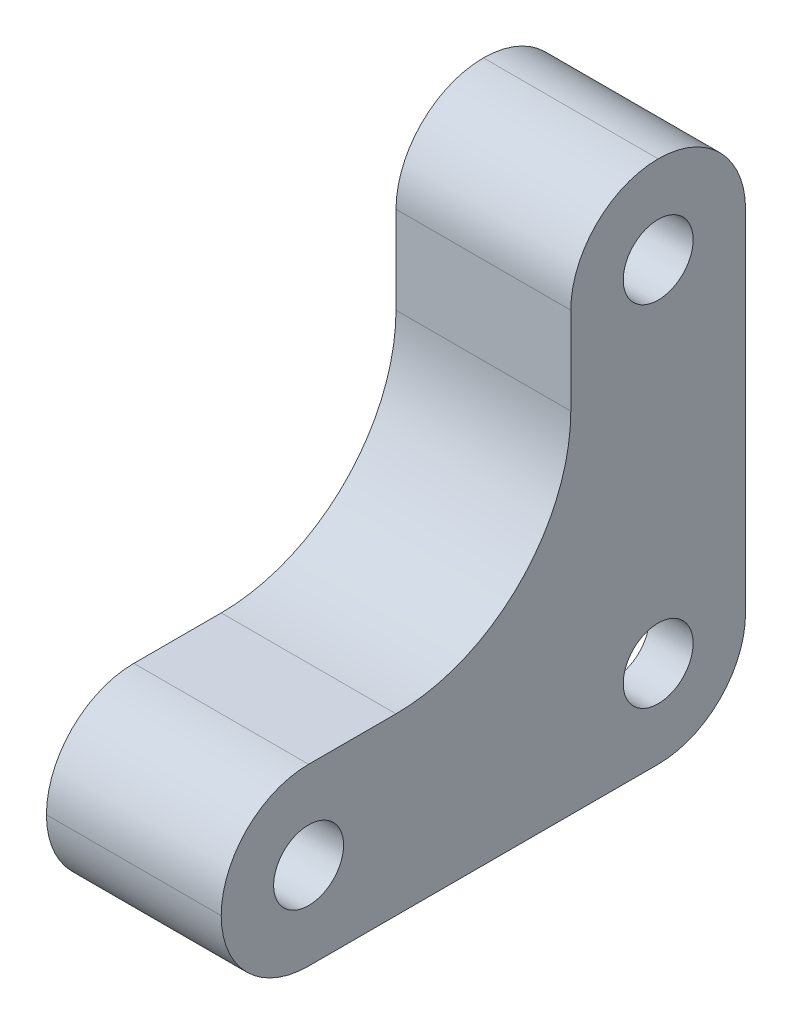
SolidWorks part; units mm, degrees
ref_plane "Front" through (0, 0, 0) normal (0, 0, 1) x (1, 0, 0)
ref_plane "Top" through (0, 0, 0) normal (0, 1, 0) x (1, 0, 0)
ref_plane "Right" through (0, 0, 0) normal (1, 0, 0) x (0, 0, -1)
sketch "Sketch1" plane through (0, 0, 0) normal (0, 1, 0) x (1, 0, 0)
  line L1 (-5, -15) -> (5, -15)
  line L2 (-5, -15) -> (-5, 15)
  line L3 (-5, 15) -> (5, 15)
  line L4 (5, -15) -> (5, 15)
  line L5 (-5, -15) -> (5, 15) construction
  line L6 (-5, 15) -> (5, -15) construction
  point P0 (0, 0)
  dimension "D1" = 10
  dimension "D2" = 30
extrude "Boss-Extrude1" add sketch "Sketch1" along normal blind 10
sketch "Sketch2" plane through (0, 10, 0) normal (0, 1, 0) x (1, 0, 0)
  line L0 (5, -15) -> (5, 15) construction
  line L1 (-5, 15) -> (5, 15)
  line L2 (-5, 15) -> (-5, 5)
  line L3 (-5, 5) -> (5, 5)
  line L4 (5, 15) -> (5, 5)
  dimension "D1" = 10
extrude "Boss-Extrude2" add sketch "Sketch2" along normal blind 20
sketch "Sketch3" plane through (5, 0, 0) normal (1, 0, 0) x (0, 0, -1)
  line L0 (-15, 10) -> (5, 10) construction
  line L1 (-15, 10) -> (-15, 0) construction
  line L2 (5, 30) -> (15, 30) construction
  line L3 (5, 30) -> (5, 10) construction
  circle A0 centre (-10, 5) radius 2
  circle A1 centre (10, 25) radius 2
  dimension "D1" = 4
  dimension "D2" = 5
  dimension "D3" = 5
  dimension "D4" = 5
  dimension "D5" = 5
extrude "Cut-Extrude1" cut sketch "Sketch3" against normal through all
fillet "Fillet1" radius 5 4 edges at (0, 30, -15) (0, 30, -5) (0, 0, 15) (0, 10, 15)
sketch "Sketch4" plane through (5, 0, 0) normal (1, 0, 0) x (0, 0, -1)
  line L0 (-10, 0) -> (15, 0) construction
  line L5 (15, 25) -> (15, 0) construction
  circle A0 centre (10, 5) radius 2
  circle A1 centre (10, 25) radius 2 construction
  point P8 (0, 0)
  point P10 (14.24, 5.5151)
  dimension "D1" = 5
  dimension "D2" = 5
fillet "Fillet2" radius 10 1 edges at (0, 10, -5)
sketch "Sketch6" plane through (0, 0, -15) normal (0, 0, -1) x (-1, 0, 0)
  line L0 (-5, 0) -> (5, 0) construction
  line L1 (-2.5, 0) -> (2.5, 0)
  line L2 (-2.5, 0) -> (-2.5, 10)
  line L3 (-2.5, 10) -> (2.5, 10)
  line L4 (2.5, 0) -> (2.5, 10)
  line L7 (-5, 25) -> (-5, 0) construction
  dimension "D1" = 5
  dimension "D2" = 2.5
  dimension "D3" = 10
extrude "Cut-Extrude3" cut sketch "Sketch6" against normal blind 10
chamfer "Chamfer1" distance 10 angle 45 2 edges at (0, 0, -5) (0, 10, -15)
extrude "Cut-Extrude4" cut sketch "Sketch4" against normal through all
fillet "Fillet3" radius 5 2 edges at (-3.75, 0, -15) (3.75, 0, -15)
